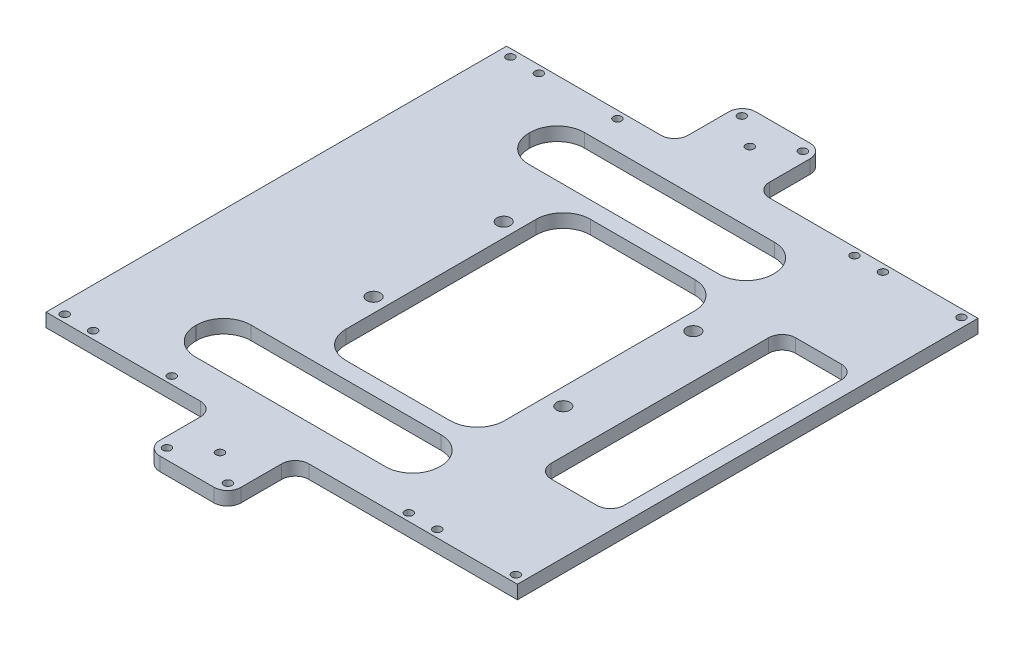
SolidWorks part; units mm, degrees
ref_plane "前视基准面" through (0, 0, 0) normal (0, 0, 1) x (1, 0, 0)
ref_plane "上视基准面" through (0, 0, 0) normal (0, 1, 0) x (1, 0, 0)
ref_plane "右视基准面" through (0, 0, 0) normal (1, 0, 0) x (0, 0, -1)
other "Configuration Table"
sketch "草图1" plane through (0, 0, 0) normal (0, 1, 0) x (1, 0, 0)
  line L0 (0, 0) -> (179.4567, 0) construction
  line L1 (-150, 150) -> (150, 150) construction
  line L2 (-150, 150) -> (-150, -150) construction
  line L3 (-150, -150) -> (150, -150) construction
  line L4 (150, 150) -> (150, -150) construction
  line L5 (-150, 150) -> (150, -150) construction
  line L6 (-150, -150) -> (150, 150) construction
  line L7 (-125, 85) -> (-67.9992, 85)
  line L9 (-125, -85) -> (-67.9992, -85)
  line L11 (-125, 85) -> (-125, -85)
  line L16 (-111.5, 85) -> (-111.5, -49915) construction
  line L17 (-27.9992, 85) -> (49.0008, 85)
  line L29 (-62.9992, 90) -> (-62.9992, 105)
  line L30 (-57.9992, 110) -> (-37.9992, 110)
  line L31 (-32.9992, 90) -> (-32.9992, 105)
  line L32 (-32.9992, -90) -> (-32.9992, -105)
  line L33 (-57.9992, -110) -> (-37.9992, -110)
  line L34 (-62.9992, -90) -> (-62.9992, -105)
  line L35 (-27.9992, -85) -> (49.0008, -85)
  line L44 (15.5008, 96) -> (15.5008, -352.075) construction
  line L46 (-144.9992, -88.2675) -> (-77.9992, -88.2675) construction
  line L47 (-144.9992, -88.2675) -> (-144.9992, -128.3094) construction
  line L48 (-144.9992, -128.3094) -> (-77.9992, -128.3094) construction
  line L49 (-77.9992, -88.2675) -> (-77.9992, -128.3094) construction
  line L57 (-77.9992, 88.2675) -> (-77.9992, 128.3094) construction
  line L58 (-144.9992, 128.3094) -> (-77.9992, 128.3094) construction
  line L59 (-144.9992, 88.2675) -> (-144.9992, 128.3094) construction
  line L60 (-144.9992, 88.2675) -> (-77.9992, 88.2675) construction
  line L61 (-17.9992, -88.2675) -> (-17.9992, -128.3) construction
  line L62 (49.0008, -128.3) -> (-17.9992, -128.3) construction
  line L63 (49.0008, 128.3) -> (-17.9992, 128.3) construction
  line L64 (49.0008, 88.2675) -> (-17.9992, 88.2675) construction
  line L65 (49.0008, 88.2675) -> (49.0008, 128.3) construction
  line L66 (49.0008, 128.3) -> (-17.9992, 128.3) construction
  line L67 (-17.9992, 88.2675) -> (-17.9992, 128.3) construction
  line L68 (49.0008, -88.2675) -> (49.0008, -128.3) construction
  line L69 (49.0008, -88.2675) -> (-17.9992, -88.2675) construction
  line L71 (-47.9992, 110) -> (-47.9992, -134.4619) construction
  line L72 (49.0008, 85) -> (49.0008, -85)
  line L73 (-12.9149, -51.3108) -> (-83.0835, -51.3108)
  line L74 (-12.9149, 71.7703) -> (-83.0835, 71.7703)
  line L75 (-2.9149, 61.7703) -> (-2.9149, 61.3108)
  line L76 (-12.9149, 51.3108) -> (-83.0835, 51.3108)
  line L77 (-93.0835, 61.7703) -> (-93.0835, 61.3108)
  line L78 (-93.0835, -61.7703) -> (-93.0835, -61.3108)
  line L79 (-2.9149, -61.7703) -> (-2.9149, -61.3108)
  line L80 (-12.9149, -71.7703) -> (-83.0835, -71.7703)
  line L81 (-69.4223, 28.3555) -> (-69.4223, -19.6445) construction
  line L82 (-15.666, 45.1305) -> (-54.2, 45.1305)
  line L83 (-5.666, 35.1305) -> (-5.666, -35.1305)
  line L84 (-15.666, -45.1305) -> (-54.2, -45.1305)
  line L85 (-64.2, 35.1305) -> (-64.2, -35.1305)
  line L86 (-69.4223, -19.6445) -> (0.5777, -19.6445) construction
  line L87 (0.5777, -19.6445) -> (0.5777, 28.3555) construction
  line L88 (0.5777, 28.3555) -> (-69.4223, 28.3555) construction
  circle A3 centre (-120.84, -82.25) radius 1.5
  circle A4 centre (-110.34, -82.25) radius 1.5
  circle A5 centre (-81.34, -82.25) radius 1.5
  circle A6 centre (-81.34, 82.25) radius 1.5
  circle A7 centre (-110.34, 82.25) radius 1.5
  circle A8 centre (-120.84, 82.25) radius 1.5
  arc A9 (-37.9992, 110) -> (-32.9992, 105) centre (-37.9992, 105) cw
  arc A10 (-62.9992, 105) -> (-57.9992, 110) centre (-57.9992, 105) cw
  arc A11 (-27.9992, 85) -> (-32.9992, 90) centre (-27.9992, 90) cw
  arc A12 (-67.9992, 85) -> (-62.9992, 90) centre (-67.9992, 90) ccw
  arc A13 (-67.9992, -85) -> (-62.9992, -90) centre (-67.9992, -90) cw
  arc A14 (-27.9992, -85) -> (-32.9992, -90) centre (-27.9992, -90) ccw
  arc A15 (-62.9992, -105) -> (-57.9992, -110) centre (-57.9992, -105) ccw
  arc A16 (-37.9992, -110) -> (-32.9992, -105) centre (-37.9992, -105) ccw
  circle A17 centre (6.16, 82.25) radius 1.5
  circle A18 centre (16.66, 82.25) radius 1.5
  circle A19 centre (45.66, 82.25) radius 1.5
  circle A20 centre (6.16, -82.25) radius 1.5
  circle A21 centre (16.66, -82.25) radius 1.5
  circle A22 centre (45.66, -82.25) radius 1.5
  circle A23 centre (-69.4223, 28.3555) radius 2.5
  circle A24 centre (0.5777, 28.3555) radius 2.5
  circle A25 centre (-69.4223, -19.6445) radius 2.5
  circle A26 centre (0.5777, -19.6445) radius 2.5
  circle A27 centre (-59.2492, -106.1) radius 1.5
  circle A28 centre (-36.7492, -106.1) radius 1.5
  circle A29 centre (-47.9992, -97.7894) radius 1.5
  circle A30 centre (-36.7492, 106.1) radius 1.5
  circle A31 centre (-59.2492, 106.1) radius 1.5
  circle A32 centre (-47.9992, 97.7894) radius 1.5
  arc A33 (-83.0835, 51.3108) -> (-93.0835, 61.3108) centre (-83.0835, 61.3108) cw
  arc A34 (-2.9149, 61.3108) -> (-12.9149, 51.3108) centre (-12.9149, 61.3108) cw
  arc A35 (-12.9149, 71.7703) -> (-2.9149, 61.7703) centre (-12.9149, 61.7703) cw
  arc A36 (-83.0835, 71.7703) -> (-93.0835, 61.7703) centre (-83.0835, 61.7703) ccw
  arc A37 (-83.0835, -51.3108) -> (-93.0835, -61.3108) centre (-83.0835, -61.3108) ccw
  arc A38 (-83.0835, -71.7703) -> (-93.0835, -61.7703) centre (-83.0835, -61.7703) cw
  arc A39 (-2.9149, -61.3108) -> (-12.9149, -51.3108) centre (-12.9149, -61.3108) ccw
  arc A40 (-12.9149, -71.7703) -> (-2.9149, -61.7703) centre (-12.9149, -61.7703) ccw
  arc A41 (-5.666, -35.1305) -> (-15.666, -45.1305) centre (-15.666, -35.1305) cw
  arc A42 (-54.2, -45.1305) -> (-64.2, -35.1305) centre (-54.2, -35.1305) cw
  arc A43 (-54.2, 45.1305) -> (-64.2, 35.1305) centre (-54.2, 35.1305) ccw
  arc A44 (-15.666, 45.1305) -> (-5.666, 35.1305) centre (-15.666, 35.1305) cw
  point P0 (0, 0)
  point P30 (-32.9992, 110)
  point P33 (-62.9992, 110)
  point P61 (-62.9992, -110)
  point P62 (-32.9992, -110)
  dimension "D7" = 3
  dimension "D12" = 5
  dimension "D17" = 22.5
  dimension "D19" = 3
  dimension "D22" = 10
  dimension "D23" = 10
  dimension "D1" = 300
  dimension "D2" = 300
  dimension "D3" = 65
  dimension "D4" = 50
  dimension "D5" = 2.75
  dimension "D6" = 4.16
  dimension "D8" = 10.5
  dimension "D9" = 29
  dimension "D10" = 30
  dimension "D11" = 15
  dimension "D13" = 67
  dimension "D14" = 9.34
  dimension "D15" = 2
  dimension "D16" = 15
  dimension "D18" = 15
  dimension "D20" = 3.9
  dimension "D21" = 8.3106
  dimension "D24" = 48
  dimension "D25" = 70
extrude "凸台-拉伸1" add sketch "草图1" along normal blind 5
sketch "草图2" plane through (0, 0, 0) normal (0, -1, 0) x (1, 0, 0)
  line L1 (21.5563, 45.1305) -> (38.4643, 45.1305)
  line L2 (16.5563, 40.1305) -> (16.5563, -40.1305)
  line L3 (21.5563, -45.1305) -> (38.4643, -45.1305)
  line L4 (43.4643, 40.1305) -> (43.4643, -40.1305)
  arc A0 (38.4643, -45.1305) -> (43.4643, -40.1305) centre (38.4643, -40.1305) ccw
  arc A1 (16.5563, -40.1305) -> (21.5563, -45.1305) centre (21.5563, -40.1305) ccw
  arc A2 (38.4643, 45.1305) -> (43.4643, 40.1305) centre (38.4643, 40.1305) cw
  arc A3 (21.5563, 45.1305) -> (16.5563, 40.1305) centre (21.5563, 40.1305) ccw
  dimension "D1" = 5
extrude "切除-拉伸1" cut sketch "草图2" against normal through all
